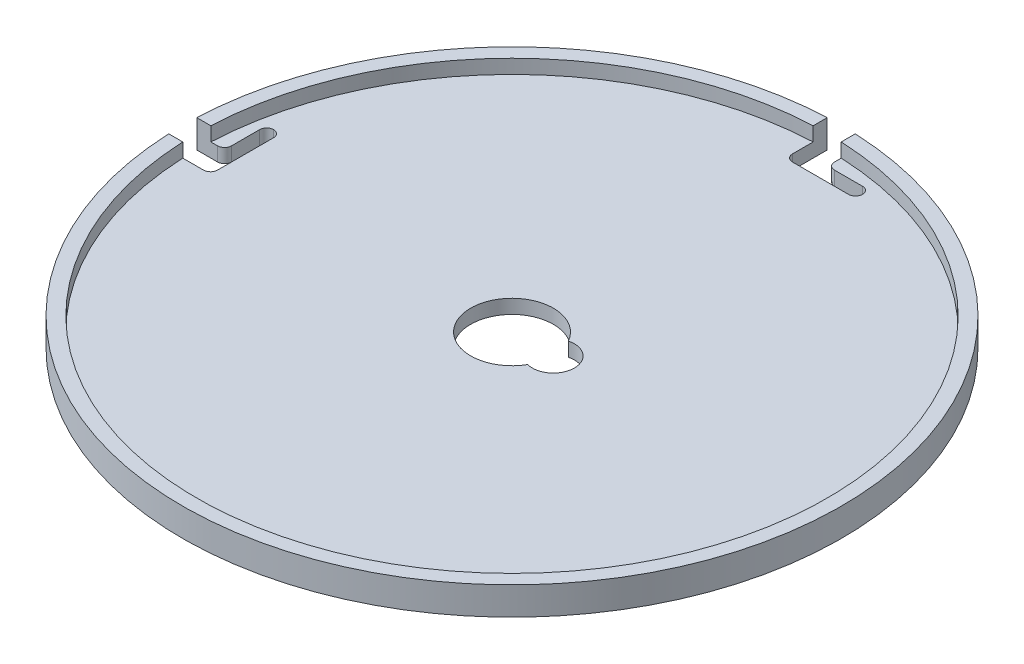
SolidWorks part; units mm, degrees
ref_plane "Front Plane" through (0, 0, 0) normal (0, 0, 1) x (1, 0, 0)
ref_plane "Top Plane" through (0, 0, 0) normal (0, 1, 0) x (1, 0, 0)
ref_plane "Right Plane" through (0, 0, 0) normal (1, 0, 0) x (0, 0, -1)
sketch "Sketch1" plane through (0, 0, 0) normal (0, 1, 0) x (1, 0, 0)
  circle A0 centre (0, 0) radius 45
  dimension "D1" = 90
extrude "Outer DIsk" add sketch "Sketch1" along normal blind 2
shell "Enclosement" thickness 2 removed face at (0, 2, 45) outward yes
sketch "Sketch2" plane through (0, 0, 0) normal (0, 1, 0) x (1, 0, 0)
  line L0 (-2, 47) -> (-2, 41)
  line L9 (-2, 47) -> (2, 47)
  line L10 (2, 47) -> (2, 43)
  line L11 (-2, 41) -> (8, 41)
  line L12 (2, 43) -> (8, 43)
  line L13 (8, 41) -> (8, 43)
  line L14 (2, 43) -> (2, 41)
  circle A1 centre (0, 0) radius 47 construction
  circle A3 centre (0, 0) radius 41 construction
  point P2 (0, 47)
  dimension "D1" = 4
  dimension "D2" = 6
  dimension "D3" = 2
  dimension "D4" = 10
extrude "Hook Release" cut sketch "Sketch2" against normal through all both and the other way through all contours L10 L9 L0 L11 L13 L12
sketch "Sketch3" plane through (0, 0, 0) normal (0, 1, 0) x (1, 0, 0)
  circle A0 centre (0, 0) radius 28.75 construction
  circle A1 centre (0, 0) radius 5.9
  circle A2 centre (5.9, 0) radius 3
  dimension "D1" = 11.8
  dimension "D3" = 6
  dimension "D2" = 5.9
pattern_circular "CirPattern1" count 2 over 90 about axis through (0, 2, 0) along (0, 1, 0) of "Hook Release"
extrude "Servo Motor Cutout" cut sketch "Sketch3" against normal through all both and the other way through all contours A2 A1 | A1 A2 | A1 A2 region at (4.4996, 0, 0) region at (7.026, 0, 0) region at (-0.586, 0, 0)
fillet "Fillet1" radius 1 8 edges at (-41, -1, 2) (-41, -1, -8) (-43, -1, -8) (-43, -1, -2) (8, -1, -41) (-2, -1, -41) (8, -1, -43) (2, -1, -43)
